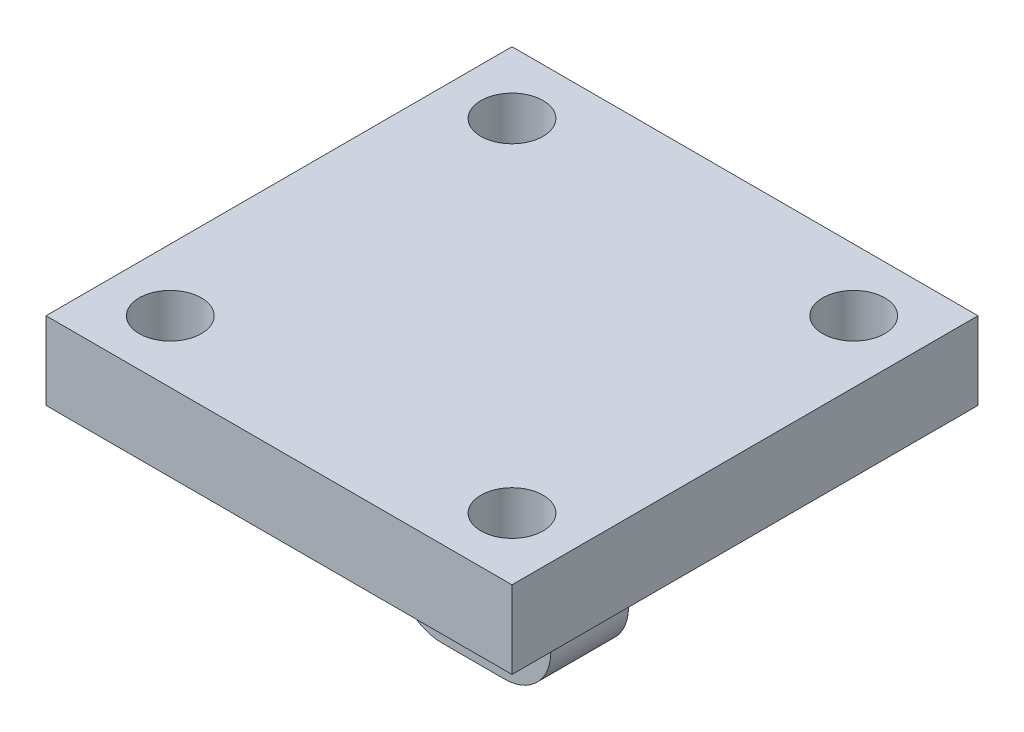
SolidWorks part; units mm, degrees
ref_plane "Front" through (0, 0, 0) normal (0, 0, 1) x (1, 0, 0)
ref_plane "Top" through (0, 0, 0) normal (0, 1, 0) x (1, 0, 0)
ref_plane "Right" through (0, 0, 0) normal (1, 0, 0) x (0, 0, -1)
sketch "Sketch2" plane through (0, 0, 0) normal (0, 0, 1) x (1, 0, 0)
  line L0 (-5, 4.24) -> (-10, 4.24) construction
  line L1 (0, 0) -> (-10, 0)
  line L2 (0, 0) -> (0, 18)
  line L3 (0, 18) -> (-10, 18)
  line L4 (-10, 0) -> (-10, 18)
  line L5 (-5, 4.24) -> (0, 4.24) construction
  circle A0 centre (-5, 4.24) radius 2
  dimension "D4" = 4
  dimension "D1" = 18
  dimension "D2" = 10
  dimension "D3" = 13.76
extrude "Boss-Extrude1" add sketch "Sketch2" along normal blind 5 contours L4 L1 L2 L3 A0 region at (-5, 9.3573, 0)
sketch "Sketch3" plane through (0, 18, 0) normal (0, 1, 0) x (1, 0, 0)
  line L1 (-20, -17.5) -> (10, -17.5)
  line L2 (-20, -17.5) -> (-20, 12.5)
  line L3 (-20, 12.5) -> (10, 12.5)
  line L4 (10, -17.5) -> (10, 12.5)
  line L7 (0, 0) -> (10, 0) construction
  line L8 (-10, 0) -> (-20, 0) construction
  line L9 (0, 0) -> (0, 12.5) construction
  line L10 (0, -5) -> (0, -17.5) construction
  dimension "D1" = 30
  dimension "D2" = 30
extrude "Boss-Extrude2" add sketch "Sketch3" against normal blind 5
fillet "Fillet1" radius 5 2 edges at (-10, 13, 2.5) (0, 13, 2.5)
fillet "Fillet2" radius 3 2 edges at (0, 0, 2.5) (-10, 0, 2.5)
sketch "Sketch4" plane through (0, 18, 0) normal (0, 1, 0) x (1, 0, 0)
  line L0 (10, -17.5) -> (10, 12.5) construction
  line L1 (10, 12.5) -> (-20, 12.5) construction
  line L2 (-20, 12.5) -> (-20, -17.5) construction
  line L3 (-20, -17.5) -> (10, -17.5) construction
  circle A0 centre (-16, 8.5) radius 2
  circle A1 centre (6, 8.5) radius 2
  circle A2 centre (6, -13.5) radius 2
  circle A3 centre (-16, -13.5) radius 2
  dimension "D1" = 4
  dimension "D2" = 4
  dimension "D3" = 4
  dimension "D4" = 4
  dimension "D5" = 4
  dimension "D6" = 4
  dimension "D7" = 4
  dimension "D8" = 4
  dimension "D9" = 4
  dimension "D10" = 4
  dimension "D11" = 4
  dimension "D12" = 4
extrude "Cut-Extrude1" cut sketch "Sketch4" against normal blind 5
